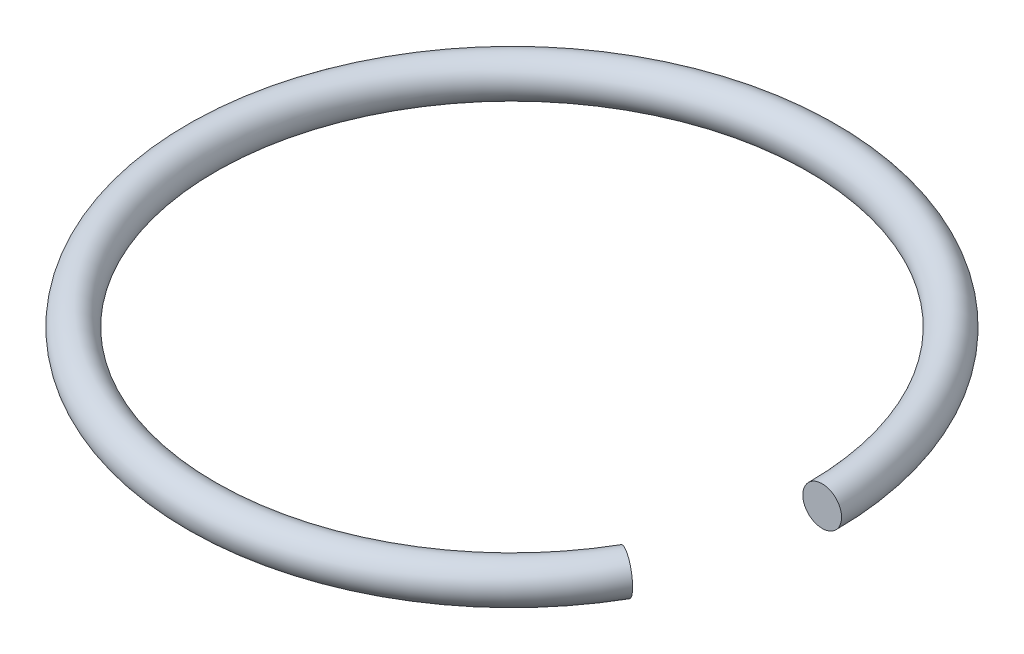
SolidWorks part; units mm, degrees
material "Alloy Steel"
ref_plane "Front Plane" through (0, 0, 0) normal (0, 0, 1) x (1, 0, 0)
ref_plane "Top Plane" through (0, 0, 0) normal (0, 1, 0) x (1, 0, 0)
ref_plane "Right Plane" through (0, 0, 0) normal (1, 0, 0) x (0, 0, -1)
sketch "Sketch1" plane through (0, 0, 0) normal (0, 0, 1) x (1, 0, 0)
  line L0 (0, 0) -> (0, 85.2237) construction
  circle A0 centre (8, 0) radius 0.5
  point P5 (0, 0)
  dimension "D2" = 1
  dimension "D1" = 16
revolve "Revolve1" add sketch "Sketch1" angle 330 about L0
ref_axis "Axis1" through (0, 13.6226, 0) along (0, -1, 0)
